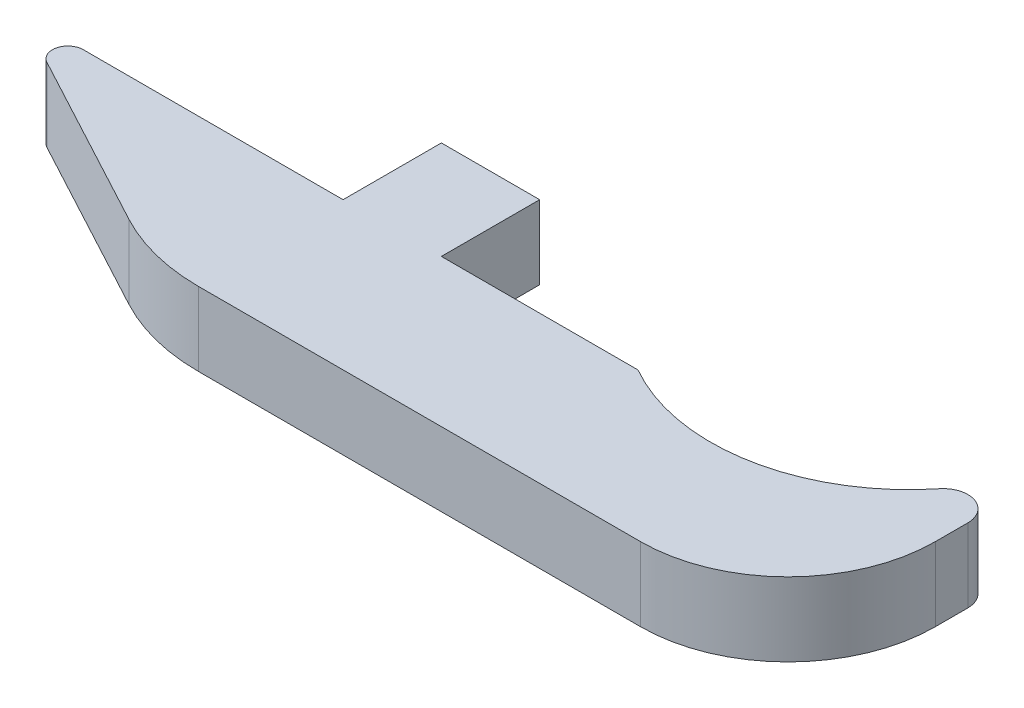
SolidWorks part; units mm, degrees
material "AISI 4130 Steel, annealed at 865C"
ref_plane "X-Y Datum" through (0, 0, 0) normal (0, 0, 1) x (1, 0, 0)
ref_plane "X-Z Datum" through (0, 0, 0) normal (0, 1, 0) x (1, 0, 0)
ref_plane "Y-Z Datum" through (0, 0, 0) normal (1, 0, 0) x (0, 0, -1)
sketch "Sketch1" plane through (0, 0, 0) normal (0, 1, 0) x (1, 0, 0)
  line L0 (20.8895, 0) -> (0, 0) construction
  line L1 (49.3776, 0) -> (0, 0)
  line L2 (49.3776, 0) -> (49.3776, 11.1252)
  line L3 (20.9296, -9.525) -> (62.2046, -9.525)
  line L4 (62.2046, 11.1252) -> (62.2046, -9.525)
  line L5 (3.175, 0) -> (20.9296, -9.525)
  circle A0 centre (49.3776, 11.1252) radius 12.827
  dimension "D3" = 25.654
  dimension "D5" = 9.525
  dimension "D1" = 49.3776
  dimension "D2" = 11.1252
  dimension "D4" = 3.175
  dimension "D6" = 41.275
extrude "Boss-Extrude1" add sketch "Sketch1" along normal blind 4.7625 contours L1 A0 region at (37.4995, 0, 4.291)
fillet "Fillet1" radius 9.525 1 edges at (62.2046, 2.3813, 9.525)
fillet "Fillet2" radius 1.5875 1 edges at (62.2046, 2.3813, -11.1252)
fillet "Fillet4" radius 12.7 1 edges at (20.9296, 2.3813, 9.525)
sketch "Sketch2" plane through (0, 0, 0) normal (0, -1, 0) x (1, 0, 0)
  line L1 (30.2875, -6.35) -> (30.2875, 0)
  line L2 (-7.0505, -6.35) -> (27.8745, -6.35) construction
  line L3 (30.2875, 0) -> (23.9375, 0)
  line L4 (30.2875, 0) -> (30.2875, -6.35)
  line L5 (30.2875, -6.35) -> (23.9375, -6.35)
  line L6 (23.9375, 0) -> (23.9375, -6.35)
  line L7 (33.5895, 0) -> (33.5895, -6.35) construction
  line M6 (3.175, 0) -> (42.9931, 0)
  dimension "D1" = 6.35
  dimension "D2" = 3.302
extrude "Boss-Extrude2" add sketch "Sketch2" against normal blind 4.7625 contours L6 L5 L1 M6 region at (27.1125, 0, -3.175)
fillet "Fillet5" radius 1 1 edges at (3.175, 2.3813, 0)
